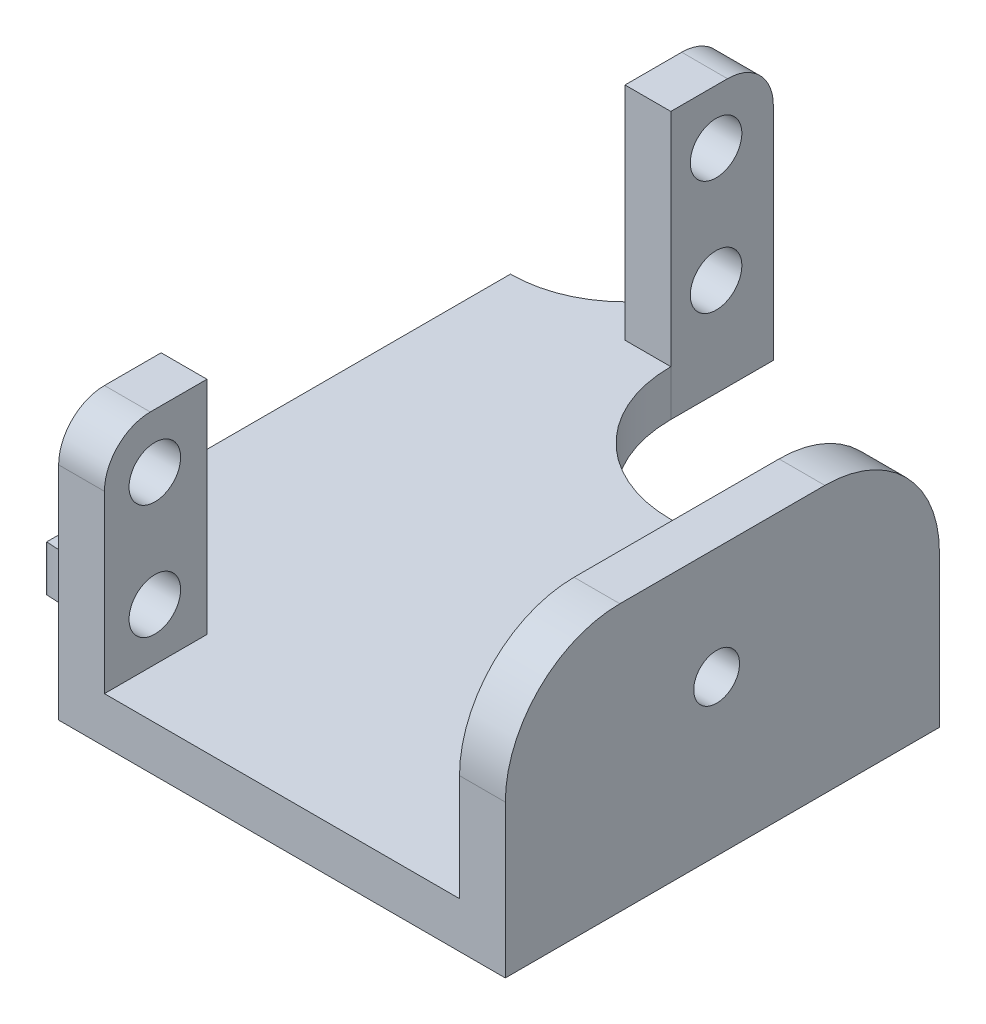
SolidWorks part; units mm, degrees
material "PLA"
ref_plane "Front Plane" through (0, 0, 0) normal (0, 0, 1) x (1, 0, 0)
ref_plane "Top Plane" through (0, 0, 0) normal (0, 1, 0) x (1, 0, 0)
ref_plane "Right Plane" through (0, 0, 0) normal (1, 0, 0) x (0, 0, -1)
sketch "Sketch1" plane through (0, 0, 0) normal (0, 1, 0) x (1, 0, 0)
  line L0 (-49, 49.45) -> (-39, 49.45)
  line L1 (-39, 49.45) -> (-39, 58.4)
  line L2 (-39, 58.4) -> (0, 58.4)
  line L3 (0, 58.4) -> (0, 0)
  line L4 (0, 0) -> (-39, 0)
  line L5 (-39, 0) -> (-39, 8.95)
  line L6 (-39, 8.95) -> (-49, 8.95)
  line L7 (-49, 8.95) -> (-49, 49.45)
  dimension "D1" = 58.4
  dimension "D2" = 49
  dimension "D3" = 10
  dimension "D4" = 8.95
  dimension "D5" = 8.95
extrude "Boss-Extrude1" add sketch "Sketch1" along normal blind 4
sketch "Sketch2" plane through (-39, 0, 0) normal (-1, 0, 0) x (0, 0, 1)
  line L0 (-58.4, 4) -> (-49.45, 4) construction
  line L1 (-8.95, 23.3) -> (0, 23.3)
  line L2 (-8.95, 23.3) -> (-8.95, 4)
  line L3 (-8.95, 4) -> (0, 4)
  line L4 (0, 23.3) -> (0, 4)
  line L5 (-58.4, 23.3) -> (-49.45, 23.3)
  line L6 (-58.4, 23.3) -> (-58.4, 4)
  line L7 (-58.4, 4) -> (-49.45, 4)
  line L8 (-49.45, 23.3) -> (-49.45, 4)
  line L9 (-58.4, 4) -> (-58.4, 0) construction
  line L10 (-49.45, 4) -> (-49.45, 0) construction
  line L11 (-8.95, 4) -> (0, 4) construction
  line L12 (0, 4) -> (0, 0) construction
  line L13 (-8.95, 4) -> (-8.95, 0) construction
  line L14 (-49.45, 4) -> (-8.95, 4) construction
  circle A0 centre (-4.4, 18.55) radius 2.25
  circle A1 centre (-4.4, 8.55) radius 2.25
  circle A2 centre (-53.4, 18.55) radius 2.25
  circle A3 centre (-53.4, 8.55) radius 2.25
  dimension "D1" = 4.5
  dimension "D2" = 4.5
  dimension "D8" = 4.5
  dimension "D9" = 4.5
  dimension "D3" = 19.3
  dimension "D4" = 10
  dimension "D5" = 3.95
  dimension "D6" = 4.55
  dimension "D7" = 3.95
  dimension "D10" = 4.55
extrude "Boss-Extrude2" add sketch "Sketch2" against normal blind 4
fillet "Fillet1" radius 10 2 edges at (-39, 2, -49.45) (-39, 2, -8.95)
fillet "Fillet2" radius 4 2 edges at (-37, 23.3, -58.4) (-37, 23.3, 0)
sketch "Sketch3" plane through (0, 0, 0) normal (1, 0, 0) x (0, 0, -1)
  line L0 (0, 4) -> (58.4, 4) construction
  line L1 (0, 23.3) -> (58.4, 23.3)
  line L2 (0, 23.3) -> (0, 4)
  line L3 (0, 4) -> (58.4, 4)
  line L4 (58.4, 23.3) -> (58.4, 4)
  line L5 (0, 4) -> (0, 0) construction
  line L6 (58.4, 4) -> (58.4, 0) construction
  circle A0 centre (18.45, 13.55) radius 2
  dimension "D4" = 4
  dimension "D1" = 19.3
  dimension "D2" = 18.45
  dimension "D3" = 9.55
extrude "Boss-Extrude3" add sketch "Sketch3" against normal blind 4
sketch "Sketch4" plane through (0, 0, 0) normal (0, -1, 0) x (1, 0, 0)
  line L0 (0, -58.4) -> (0, -37.9)
  line L1 (0, 0) -> (0, -58.4) construction
  line L2 (0, -37.9) -> (-23.45, -37.9)
  line L3 (0, -58.4) -> (-35, -58.4)
  line L4 (0, -58.4) -> (-39, -58.4) construction
  line L6 (-35, -58.4) -> (-35, -49.45)
  arc A2 (-35, -49.45) -> (-23.45, -37.9) centre (-23.45, -49.45) cw
  dimension "D3" = 23.45
  dimension "D1" = 20.5
  dimension "D2" = 35
  dimension "D4" = 8.95
extrude "Cut-Extrude1" cut sketch "Sketch4" against normal up to next
fillet "Fillet3" radius 10 1 edges at (-2, 23.3, -37.9)
fillet "Fillet4" radius 10 1 edges at (-2, 23.3, 0)
